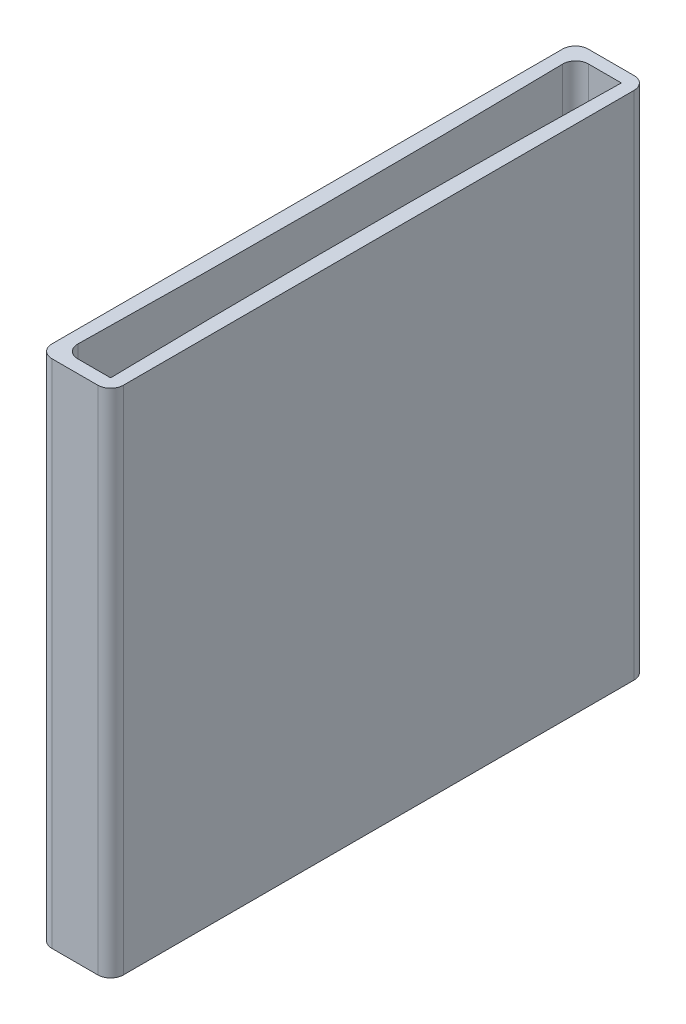
SolidWorks part; units mm, degrees
ref_plane "Face" through (0, 0, 0) normal (0, 0, 1) x (1, 0, 0)
ref_plane "Dessus" through (0, 0, 0) normal (0, 1, 0) x (1, 0, 0)
ref_plane "Droite" through (0, 0, 0) normal (1, 0, 0) x (0, 0, -1)
sketch "Esquisse1" plane through (0, 0, 0) normal (0, 1, 0) x (1, 0, 0)
  line L1 (-0.9, 10) -> (0.9, 10)
  line L2 (-0.9, 10) -> (-0.9, -10) construction
  line L3 (-0.9, -10) -> (0.9, -10)
  line L4 (0.9, 10) -> (0.9, -10)
  line L5 (-0.9, 10) -> (0.9, -10) construction
  line L6 (-0.9, -10) -> (0.9, 10) construction
  line L7 (0, 10) -> (0, 13.5212) construction
  spline S0 degree 1 poles (-0.9, 10) (-0.9, -10) knots 0 0 1 1
  point P0 (0, 0)
  dimension "D1" = 1.8
  dimension "D2" = 20
extrude "Extru.-Mince1" add sketch "Esquisse1" along normal blind 20 thin thin type one direction wall 0.5
sketch "Esquisse2" plane through (0, 0, 0) normal (0, -1, 0) x (1, 0, 0)
  line L0 (-0.9, 10) -> (-0.9, -10)
  line L1 (-0.9, 0) -> (0.9, 0) construction
  line L2 (0.9, 10) -> (0.9, -10) construction
  line L3 (0, 0) -> (0, 3.8005) construction
  arc A0 (-0.9, 10) -> (-0.9, -10) centre (-500.85, 0) cw
  point P8 (-0.8, 0)
  dimension "D1" = 0.8
extrude "Boss.-Extru.1" add sketch "Esquisse2" against normal up to vertex (20 mm away) up to point (-1.4, 20, -10.5)
mirror "Symétrie1" about plane through (0, 0, 0) normal (1, 0, 0) of "Boss.-Extru.1"
fillet "Congé1" radius 0.5 6 edges at (1.4, 10, 10.5) (-1.4, 10, 10.5) (-0.9, 10, 10) (-0.9, 10, -10) (1.4, 10, -10.5) (-1.4, 10, -10.5)
